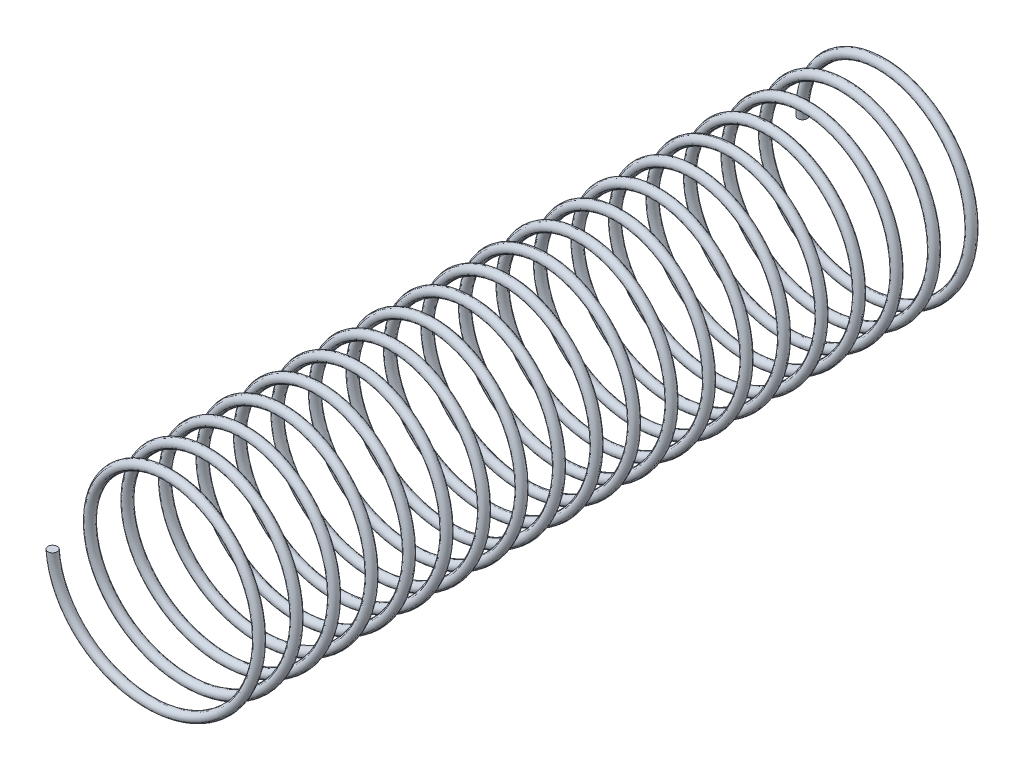
SolidWorks part; units mm, degrees
ref_plane "Front Plane" through (0, 0, 0) normal (0, 0, 1) x (1, 0, 0)
ref_plane "Top Plane" through (0, 0, 0) normal (0, 1, 0) x (1, 0, 0)
ref_plane "Right Plane" through (0, 0, 0) normal (1, 0, 0) x (0, 0, -1)
sketch "Sketch1" plane through (0, 0, 0) normal (0, 0, 1) x (1, 0, 0)
  circle A0 centre (0, 0) radius 3.175
  dimension "D1" = 6.35
curve "Helix/Spiral1" pitch 1.27 height 25.4 radius 3.175 left hand yes centre (0, 0, 0) axis (0, 0, 1) start towards (-1, 0, 0)
sketch "Sketch2" plane through (0, 0, 0) normal (0, 1, 0) x (1, 0, 0)
  circle A0 centre (-3.175, 0) radius 0.1588
  spline S0 degree 3 poles (-3.175, 0) (-3.175, -0.0263) (-3.0097, -0.0795) (-2.3035, -0.1587) (-1.2467, -0.2381) (0, -0.3175) (1.2467, -0.3969) (2.3035, -0.4762) (3.0097, -0.5556) (3.2577, -0.635) (3.0097, -0.7144) (2.3035, -0.7937) (0.8944, -0.8996) (-0.8944, -1.0054) (-2.3035, -1.1112) (-3.0097, -1.1906) (-3.2577, -1.27) (-3.0097, -1.3494) (-2.3035, -1.4287) (-0.8944, -1.5346) (0.8944, -1.6404) (2.3035, -1.7462) (3.0097, -1.8256) (3.2577, -1.905) (3.0097, -1.9844) (2.3035, -2.0637) (0.8944, -2.1696) (-0.8944, -2.2754) (-2.3035, -2.3812) (-3.0097, -2.4606) (-3.2577, -2.54) (-3.0097, -2.6194) (-2.3035, -2.6987) (-0.8944, -2.8046) (0.8944, -2.9104) (2.3035, -3.0163) (3.0097, -3.0956) (3.2577, -3.175) (3.0097, -3.2544) (2.3035, -3.3337) (0.8944, -3.4396) (-0.8944, -3.5454) (-2.3035, -3.6513) (-3.0097, -3.7306) (-3.2577, -3.81) (-3.0097, -3.8894) (-2.3035, -3.9687) (-0.8944, -4.0746) (0.8944, -4.1804) (2.3035, -4.2862) (3.0097, -4.3656) (3.2577, -4.445) (3.0097, -4.5244) (2.3035, -4.6037) (0.8944, -4.7096) (-0.8944, -4.8154) (-2.3035, -4.9212) (-3.0097, -5.0006) (-3.2577, -5.08) (-3.0097, -5.1594) (-2.3035, -5.2387) (-0.8944, -5.3446) (0.8944, -5.4504) (2.3035, -5.5562) (3.0097, -5.6356) (3.2577, -5.715) (3.0097, -5.7944) (2.3035, -5.8737) (0.8944, -5.9796) (-0.8944, -6.0854) (-2.3035, -6.1912) (-3.0097, -6.2706) (-3.2577, -6.35) (-3.0097, -6.4294) (-2.3035, -6.5087) (-0.8944, -6.6146) (0.8944, -6.7204) (2.3035, -6.8262) (3.0097, -6.9056) (3.2577, -6.985) (3.0097, -7.0644) (2.3035, -7.1437) (0.8944, -7.2496) (-0.8944, -7.3554) (-2.3035, -7.4612) (-3.0097, -7.5406) (-3.2577, -7.62) (-3.0097, -7.6994) (-2.3035, -7.7787) (-0.8944, -7.8846) (0.8944, -7.9904) (2.3035, -8.0962) (3.0097, -8.1756) (3.2577, -8.255) (3.0097, -8.3344) (2.3035, -8.4137) (0.8944, -8.5196) (-0.8944, -8.6254) (-2.3035, -8.7312) (-3.0097, -8.8106) (-3.2577, -8.89) (-3.0097, -8.9694) (-2.3035, -9.0487) (-0.8944, -9.1546) (0.8944, -9.2604) (2.3035, -9.3662) (3.0097, -9.4456) (3.2577, -9.525) (3.0097, -9.6044) (2.3035, -9.6837) (0.8944, -9.7896) (-0.8944, -9.8954) (-2.3035, -10.0012) (-3.0097, -10.0806) (-3.2577, -10.16) (-3.0097, -10.2394) (-2.3035, -10.3187) (-0.8944, -10.4246) (0.8944, -10.5304) (2.3035, -10.6362) (3.0097, -10.7156) (3.2577, -10.795) (3.0097, -10.8744) (2.3035, -10.9537) (0.8944, -11.0596) (-0.8944, -11.1654) (-2.3035, -11.2712) (-3.0097, -11.3506) (-3.2577, -11.43) (-3.0097, -11.5094) (-2.3035, -11.5887) (-0.8944, -11.6946) (0.8944, -11.8004) (2.3035, -11.9062) (3.0097, -11.9856) (3.2577, -12.065) (3.0097, -12.1444) (2.3035, -12.2237) (0.8944, -12.3296) (-0.8944, -12.4354) (-2.3035, -12.5412) (-3.0097, -12.6206) (-3.2577, -12.7) (-3.0097, -12.7794) (-2.3035, -12.8587) (-0.8944, -12.9646) (0.8944, -13.0704) (2.3035, -13.1762) (3.0097, -13.2556) (3.2577, -13.335) (3.0097, -13.4144) (2.3035, -13.4937) (0.8944, -13.5996) (-0.8944, -13.7054) (-2.3035, -13.8112) (-3.0097, -13.8906) (-3.2577, -13.97) (-3.0097, -14.0494) (-2.3035, -14.1287) (-0.8944, -14.2346) (0.8944, -14.3404) (2.3035, -14.4462) (3.0097, -14.5256) (3.2577, -14.605) (3.0097, -14.6844) (2.3035, -14.7637) (0.8944, -14.8696) (-0.8944, -14.9754) (-2.3035, -15.0812) (-3.0097, -15.1606) (-3.2577, -15.24) (-3.0097, -15.3194) (-2.3035, -15.3987) (-0.8944, -15.5046) (0.8944, -15.6104) (2.3035, -15.7162) (3.0097, -15.7956) (3.2577, -15.875) (3.0097, -15.9544) (2.3035, -16.0337) (0.8944, -16.1396) (-0.8944, -16.2454) (-2.3035, -16.3512) (-3.0097, -16.4306) (-3.2577, -16.51) (-3.0097, -16.5894) (-2.3035, -16.6687) (-0.8944, -16.7746) (0.8944, -16.8804) (2.3035, -16.9862) (3.0097, -17.0656) (3.2577, -17.145) (3.0097, -17.2244) (2.3035, -17.3037) (0.8944, -17.4096) (-0.8944, -17.5154) (-2.3035, -17.6212) (-3.0097, -17.7006) (-3.2577, -17.78) (-3.0097, -17.8594) (-2.3035, -17.9387) (-0.8944, -18.0446) (0.8944, -18.1504) (2.3035, -18.2562) (3.0097, -18.3356) (3.2577, -18.415) (3.0097, -18.4944) (2.3035, -18.5737) (0.8944, -18.6796) (-0.8944, -18.7854) (-2.3035, -18.8912) (-3.0097, -18.9706) (-3.2577, -19.05) (-3.0097, -19.1294) (-2.3035, -19.2087) (-0.8944, -19.3146) (0.8944, -19.4204) (2.3035, -19.5262) (3.0097, -19.6056) (3.2577, -19.685) (3.0097, -19.7644) (2.3035, -19.8437) (0.8944, -19.9496) (-0.8944, -20.0554) (-2.3035, -20.1612) (-3.0097, -20.2406) (-3.2577, -20.32) (-3.0097, -20.3994) (-2.3035, -20.4787) (-0.8944, -20.5846) (0.8944, -20.6904) (2.3035, -20.7962) (3.0097, -20.8756) (3.2577, -20.955) (3.0097, -21.0344) (2.3035, -21.1137) (0.8944, -21.2196) (-0.8944, -21.3254) (-2.3035, -21.4312) (-3.0097, -21.5106) (-3.2577, -21.59) (-3.0097, -21.6694) (-2.3035, -21.7487) (-0.8944, -21.8546) (0.8944, -21.9604) (2.3035, -22.0662) (3.0097, -22.1456) (3.2577, -22.225) (3.0097, -22.3044) (2.3035, -22.3837) (0.8944, -22.4896) (-0.8944, -22.5954) (-2.3035, -22.7012) (-3.0097, -22.7806) (-3.2577, -22.86) (-3.0097, -22.9394) (-2.3035, -23.0187) (-0.8944, -23.1246) (0.8944, -23.2304) (2.3035, -23.3362) (3.0097, -23.4156) (3.2577, -23.495) (3.0097, -23.5744) (2.3035, -23.6537) (0.8944, -23.7596) (-0.8944, -23.8654) (-2.3035, -23.9712) (-3.0097, -24.0506) (-3.2577, -24.13) (-3.0097, -24.2094) (-2.3035, -24.2888) (-0.8944, -24.3946) (0.8944, -24.5004) (2.3035, -24.6063) (3.0097, -24.6856) (3.2577, -24.765) (3.0097, -24.8444) (2.3035, -24.9238) (1.2467, -25.0031) (0, -25.0825) (-1.2467, -25.1619) (-2.3035, -25.2413) (-3.0097, -25.3205) (-3.175, -25.3737) (-3.175, -25.4) knots 0 0 0 0 0.003125 0.00625 0.009375 0.0125 0.015625 0.01875 0.021875 0.025 0.028125 0.03125 0.034375 0.040625 0.04375 0.046875 0.05 0.053125 0.05625 0.059375 0.065625 0.06875 0.071875 0.075 0.078125 0.08125 0.084375 0.090625 0.09375 0.096875 0.1 0.103125 0.10625 0.109375 0.115625 0.11875 0.121875 0.125 0.128125 0.13125 0.134375 0.140625 0.14375 0.146875 0.15 0.153125 0.15625 0.159375 0.165625 0.16875 0.171875 0.175 0.178125 0.18125 0.184375 0.190625 0.19375 0.196875 0.2 0.203125 0.20625 0.209375 0.215625 0.21875 0.221875 0.225 0.228125 0.23125 0.234375 0.240625 0.24375 0.246875 0.25 0.253125 0.25625 0.259375 0.265625 0.26875 0.271875 0.275 0.278125 0.28125 0.284375 0.290625 0.29375 0.296875 0.3 0.303125 0.30625 0.309375 0.315625 0.31875 0.321875 0.325 0.328125 0.33125 0.334375 0.340625 0.34375 0.346875 0.35 0.353125 0.35625 0.359375 0.365625 0.36875 0.371875 0.375 0.378125 0.38125 0.384375 0.390625 0.39375 0.396875 0.4 0.403125 0.40625 0.409375 0.415625 0.41875 0.421875 0.425 0.428125 0.43125 0.434375 0.440625 0.44375 0.446875 0.45 0.453125 0.45625 0.459375 0.465625 0.46875 0.471875 0.475 0.478125 0.48125 0.484375 0.490625 0.49375 0.496875 0.5 0.503125 0.50625 0.509375 0.515625 0.51875 0.521875 0.525 0.528125 0.53125 0.534375 0.540625 0.54375 0.546875 0.55 0.553125 0.55625 0.559375 0.565625 0.56875 0.571875 0.575 0.578125 0.58125 0.584375 0.590625 0.59375 0.596875 0.6 0.603125 0.60625 0.609375 0.615625 0.61875 0.621875 0.625 0.628125 0.63125 0.634375 0.640625 0.64375 0.646875 0.65 0.653125 0.65625 0.659375 0.665625 0.66875 0.671875 0.675 0.678125 0.68125 0.684375 0.690625 0.69375 0.696875 0.7 0.703125 0.70625 0.709375 0.715625 0.71875 0.721875 0.725 0.728125 0.73125 0.734375 0.740625 0.74375 0.746875 0.75 0.753125 0.75625 0.759375 0.765625 0.76875 0.771875 0.775 0.778125 0.78125 0.784375 0.790625 0.79375 0.796875 0.8 0.803125 0.80625 0.809375 0.815625 0.81875 0.821875 0.825 0.828125 0.83125 0.834375 0.840625 0.84375 0.846875 0.85 0.853125 0.85625 0.859375 0.865625 0.86875 0.871875 0.875 0.878125 0.88125 0.884375 0.890625 0.89375 0.896875 0.9 0.903125 0.90625 0.909375 0.915625 0.91875 0.921875 0.925 0.928125 0.93125 0.934375 0.940625 0.94375 0.946875 0.95 0.953125 0.95625 0.959375 0.965625 0.96875 0.971875 0.975 0.978125 0.98125 0.984375 0.9875 0.990625 0.99375 0.996875 1 1 1 1 construction
  dimension "D1" = 0.3175
sweep "Sweep1" add profiles "Sketch2" path "Helix/Spiral1"
